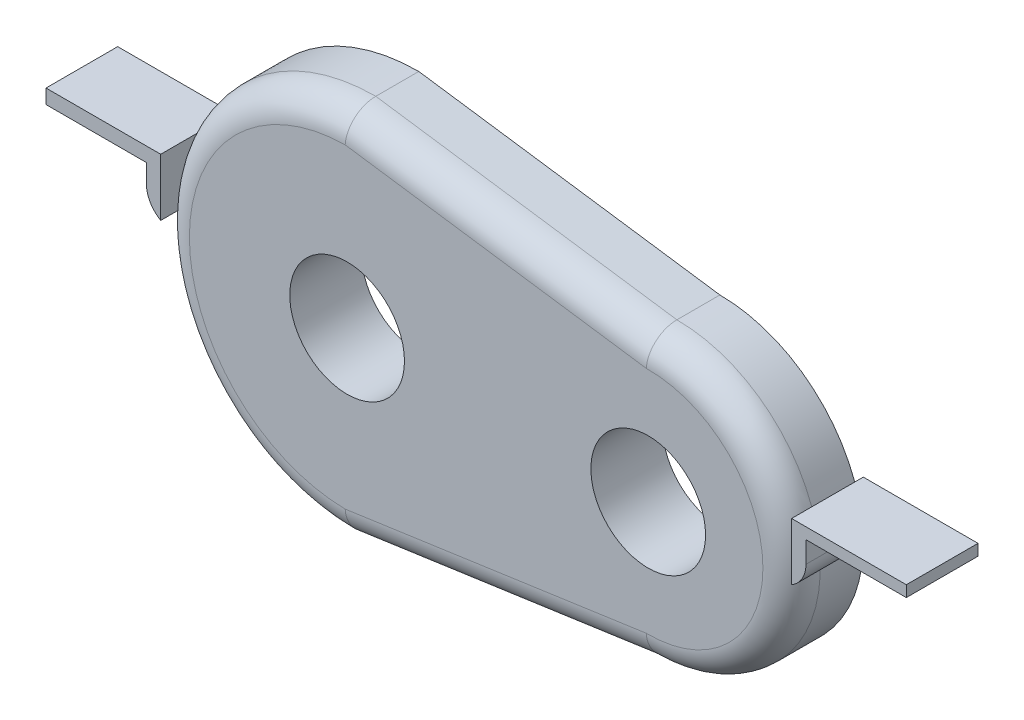
SolidWorks part; units mm, degrees
ref_plane "Front Plane" through (0, 0, 0) normal (0, 0, 1) x (1, 0, 0)
ref_plane "Top Plane" through (0, 0, 0) normal (0, 1, 0) x (1, 0, 0)
ref_plane "Right Plane" through (0, 0, 0) normal (1, 0, 0) x (0, 0, -1)
sketch "Sketch1" plane through (0, 0, 0) normal (0, 0, 1) x (1, 0, 0)
  line L0 (-61.9629, 65) -> (43.0371, 50)
  line L1 (-61.9629, -65) -> (43.0371, -50)
  arc A0 (-61.9629, 65) -> (-61.9629, -65) centre (-61.9629, 0) ccw
  arc A1 (43.0371, -50) -> (43.0371, 50) centre (43.0371, 0) ccw
  circle A2 centre (43.0371, 0) radius 20
  circle A3 centre (-61.9629, 0) radius 20
  dimension "D2" = 130
  dimension "D3" = 100
  dimension "D4" = 40
  dimension "D5" = 40
  dimension "D1" = 105
extrude "Boss-Extrude1" add sketch "Sketch1" along normal blind 25
fillet "Fillet1" radius 10 4 edges at (93.0371, 0, 25) (-9.4629, -57.5, 25) (-126.9629, 0, 25) (-9.4629, 57.5, 25)
sketch "Sketch3" plane through (0, 0, 25) normal (0, 0, 1) x (1, 0, 0)
  line L0 (93.0371, 0) -> (93.0371, 20)
  line L1 (93.0371, 20) -> (133.0371, 20)
  line L2 (133.0371, 20) -> (133.0371, 16.1048)
  line L3 (133.0371, 16.1048) -> (98.0371, 16.1048)
  line L4 (98.0371, 16.1048) -> (98.0371, 0)
  line L5 (98.0371, 0) -> (93.0371, 0)
  arc A0 (43.0371, -50) -> (43.0371, 50) centre (43.0371, 0) ccw construction
  dimension "D1" = 35
  dimension "D2" = 40
  dimension "D3" = 5
  dimension "D4" = 20
extrude "Boss-Extrude2" add sketch "Sketch3" against normal blind 25 separate body
fillet "Fillet2" radius 10 1 edges at (98.0371, 0, 12.5)
sketch "Sketch4" plane through (0, 0, 25) normal (0, 0, 1) x (1, 0, 0)
  line L0 (-126.9629, 0) -> (-131.9629, 0)
  line L1 (-131.9629, 0) -> (-131.9629, 15)
  line L2 (-131.9629, 15) -> (-166.9629, 15)
  line L3 (-166.9629, 15) -> (-166.9629, 20)
  line L4 (-166.9629, 20) -> (-126.9629, 20)
  line L5 (-126.9629, 20) -> (-126.9629, 0)
  arc A0 (-61.9629, 65) -> (-61.9629, -65) centre (-61.9629, 0) ccw construction
  dimension "D1" = 40
  dimension "D2" = 5
  dimension "D3" = 20
  dimension "D4" = 5
extrude "Boss-Extrude3" add sketch "Sketch4" against normal blind 25 separate body
fillet "Fillet3" radius 10 1 edges at (-131.9629, 0, 12.5)
